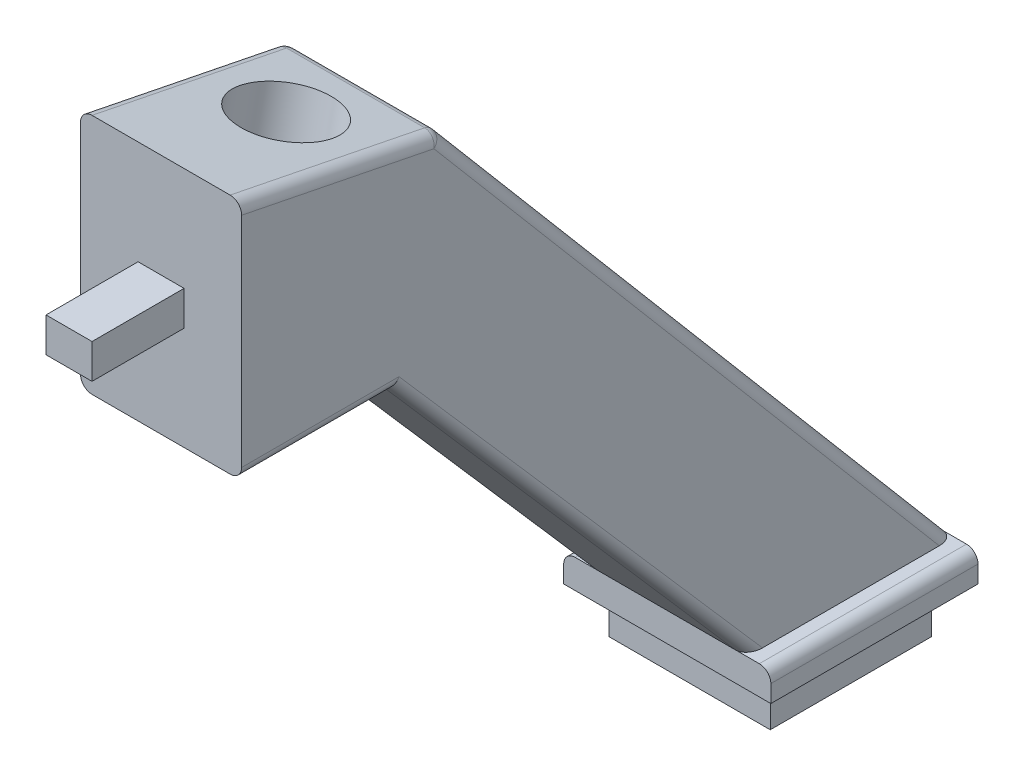
SolidWorks part; units mm, degrees
ref_plane "Front Plane" through (0, 0, 0) normal (0, 0, 1) x (1, 0, 0)
ref_plane "Top Plane" through (0, 0, 0) normal (0, 1, 0) x (1, 0, 0)
ref_plane "Right Plane" through (0, 0, 0) normal (1, 0, 0) x (0, 0, -1)
sketch "Sketch2" plane through (0, 0, 0) normal (0, 1, 0) x (1, 0, 0)
  line L2 (7, 7) -> (-7, 7)
  line L3 (-7, 7) -> (-7, -7)
  line L4 (-7, -7) -> (7, -7)
  line L5 (7, -7) -> (7, 7)
  point P4 (0, 0)
  point P8 (0, 0)
  point P11 (0, 7)
extrude "Boss-Extrude1" add sketch "Sketch2" against normal blind 4 and the other way blind 2.5
sketch "Sketch7" plane through (0, 0, 0) normal (0, 0, 1) x (1, 0, 0)
  line L0 (-6.0346, 0) -> (-4.0346, 0)
  line L2 (0, -33.0044) -> (0, 33.0044) construction
  line L3 (-6.0346, 0) -> (-6.0346, -0.5)
  line L8 (-6.0346, -0.5) -> (-4.0346, -0.5)
  line L9 (-4.0346, -0.5) -> (-4.0346, 0)
  line L10 (4.0346, -0.5) -> (4.0346, 0)
  line L11 (6.0346, -0.5) -> (4.0346, -0.5)
  line L12 (6.0346, 0) -> (6.0346, -0.5)
  line L13 (6.0346, 0) -> (4.0346, 0)
  dimension "D1" = 2
  dimension "D2" = 0.5
sketch "Sketch11" plane through (0, 0, 0) normal (0, 1, 0) x (1, 0, 0)
  line L0 (-8.9488, -8.9993) -> (-8.9488, 9.0007)
  line L1 (-8.9488, 9.0007) -> (9.0512, 9.0007)
  line L2 (-8.9488, -8.9993) -> (9.0512, -8.9993)
  line L3 (9.0512, -8.9993) -> (9.0512, 9.0007)
  dimension "D1" = 18
  dimension "D2" = 18
extrude "Boss-Extrude4" add sketch "Sketch11" along normal blind 2.5
sketch "Sketch3" plane through (0, 0, 0) normal (0, 1, 0) x (1, 0, 0)
  line L0 (2.98, 3.0412) -> (2.98, -2.9588)
  line L2 (2.98, 3.0412) -> (-3.02, 3.0412)
  line L3 (-3.02, 3.0412) -> (-3.02, -2.9588)
  line L4 (-3.02, -2.9588) -> (2.98, -2.9588)
  dimension "D1" = 6
  dimension "D2" = 6
extrude "Cut-Extrude5" cut sketch "Sketch3" against normal blind 4 and the other way blind 4
sketch "Sketch13" plane through (0, 0, 0) normal (1, 0, 0) x (0, 0, -1)
  line L1 (-39.7149, 37.7068) -> (-52.9339, 37.7068)
  line L2 (0, 0) -> (0, 2.5)
  line L3 (0, 2.5) -> (-9, 2.5)
  line L4 (0, 2.5) -> (9, 2.5)
  line L5 (-9, 2.5) -> (-39.7149, 37.7068)
  line L6 (-35.6901, 55.251) -> (9, 2.5)
  line L9 (-52.9339, 37.7068) -> (-52.9339, 58.7068)
  line L10 (-52.9339, 58.7068) -> (-35.6901, 55.251)
  point P3 (-39.7149, 37.7068)
  point P4 (-35.6901, 55.251)
  dimension "D1" = 18
  dimension "D2" = 21
extrude "Boss-Extrude5" add sketch "Sketch13" along normal blind 7 and the other way blind 7 contours L3 L5 L1 L9 L10 L6 L4
sketch "Sketch16" plane through (0, 0, 0) normal (1, 0, 0) x (0, 0, -1)
  line L0 (0, 0) -> (0.0003, 2.5)
  line L1 (-7, 0) -> (7, 0) construction
  line L2 (-8.9993, 2.5) -> (9, 2.5) construction
  line L3 (0.0003, 2.5) -> (3.0014, 2.5)
  line L4 (0.0003, 2.5) -> (-2.9997, 2.5)
  line L5 (-2.9997, 2.5) -> (-42.3379, 42.4659)
  line L6 (-42.3379, 42.4659) -> (-42.3379, 48.4659)
  line L7 (-42.3379, 48.4659) -> (3.0014, 2.5)
  dimension "D1" = 3
  dimension "D2" = 3.0011
  dimension "D3" = 6
extrude "Cut-Extrude8" cut sketch "Sketch16" against normal blind 3 and the other way blind 3 contours L4 L5 L6 L7 L3
sketch "Sketch52" plane through (0, 0, 0) normal (1, 0, 0) x (0, 0, -1)
  line L0 (-41.0385, 61.3626) -> (-48.8166, 24.8846)
sweep "Cut-Sweep4" cut path "Sketch52" circular profile diameter 8 parameters "D3"=8
fillet "Fillet1" radius 1 11 edges at (7, 20.1034, 24.3575) (-8.9488, 2.5, -0.0007) (9.0512, 2.5, -0.0007) (-7, 28.8755, 13.3451) (7, 37.7068, 46.3244) (-7, 37.7068, 46.3244) (-7, 20.1034, 24.3575) (7, 28.8755, 13.3451) (7, 56.9789, 44.312) (-7, 56.9789, 44.312) (0, 55.251, 35.6901)
sketch "Sketch59" plane through (0, 0, 0) normal (1, 0, 0) x (0, 0, -1)
  line L0 (-52.9339, 48.1883) -> (-52.9339, 49.6883)
  line L1 (-52.9339, 37.7068) -> (-52.9339, 58.7068) construction
  line L2 (-52.9339, 48.1883) -> (-52.9339, 46.6883)
  line L3 (-52.9339, 49.6883) -> (-60.9339, 49.6883)
  line L4 (-60.9339, 49.6883) -> (-60.9339, 46.6883)
  line L5 (-60.9339, 46.6883) -> (-52.9339, 46.6883)
  point P4 (-52.9339, 48.1883)
  dimension "D1" = 3
  dimension "D2" = 8
  dimension "D3" = 1.5
extrude "Boss-Extrude6" add sketch "Sketch59" along normal blind 2 and the other way blind 2 separate body
